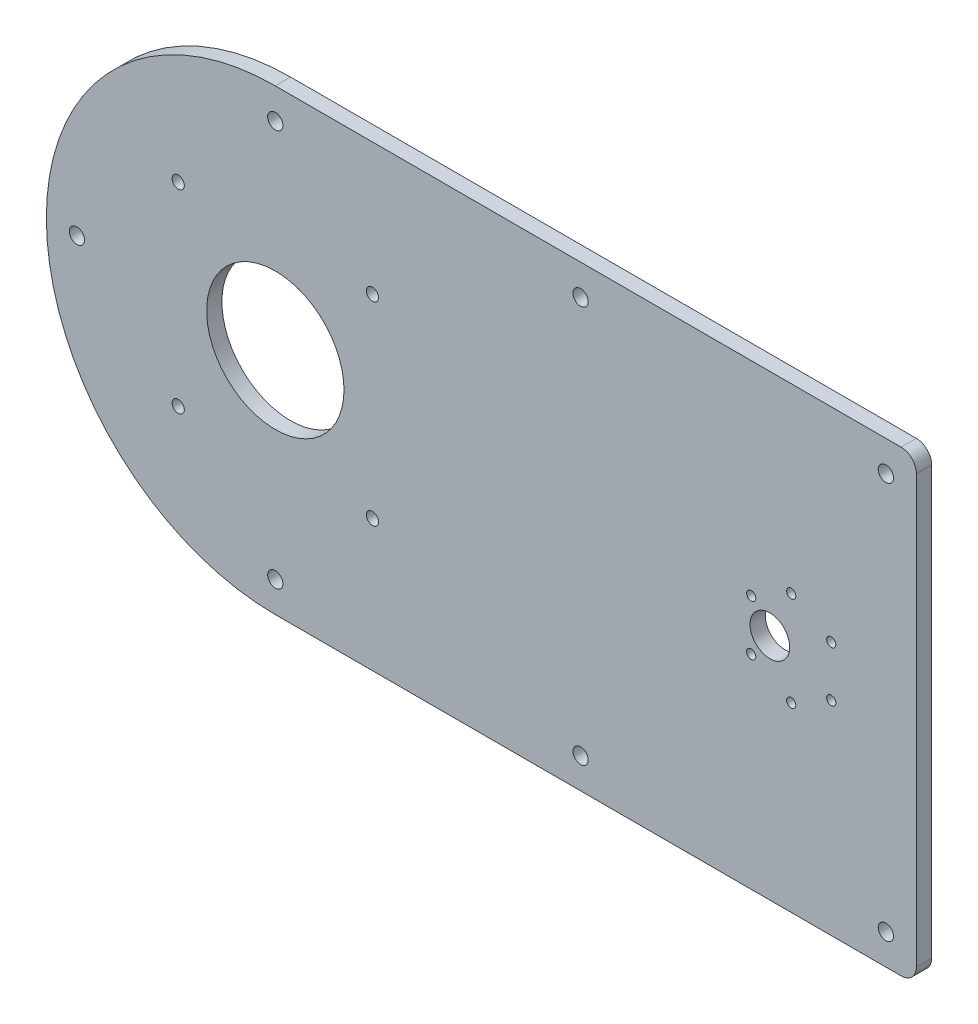
SolidWorks part; units mm, degrees
ref_plane "Front Plane" through (0, 0, 0) normal (0, 0, 1) x (1, 0, 0)
ref_plane "Top Plane" through (0, 0, 0) normal (0, 1, 0) x (1, 0, 0)
ref_plane "Right Plane" through (0, 0, 0) normal (1, 0, 0) x (0, 0, -1)
sketch "Sketch1" plane through (0, 0, 0) normal (0, 0, 1) x (1, 0, 0)
  line L1 (30.0007, 92.5455) -> (235.0007, 92.5455)
  line L3 (30.0007, -57.4545) -> (235.0007, -57.4545)
  line L4 (240.0007, 87.5455) -> (240.0007, -52.4545)
  arc A0 (235.0007, -57.4545) -> (240.0007, -52.4545) centre (235.0007, -52.4545) ccw
  arc A1 (235.0007, 92.5455) -> (240.0007, 87.5455) centre (235.0007, 87.5455) cw
  arc A2 (30.0007, 92.5455) -> (30.0007, -57.4545) centre (30.0007, 17.5455) ccw
  circle A7 centre (-34.9993, 17.5455) radius 2.5
  circle A10 centre (30.0007, -47.4545) radius 2.5
  circle A11 centre (30.0007, 82.5455) radius 2.5
  circle A12 centre (230.0007, -47.4545) radius 2.5
  circle A13 centre (230.0007, 82.5455) radius 2.5
  circle A15 centre (130.0007, 82.5455) radius 2.5
  circle A16 centre (130.0007, -47.4545) radius 2.5
  circle A18 centre (30.0007, 17.5455) radius 22.5
  circle A23 centre (61.8157, 49.3605) radius 2
  circle A24 centre (61.8157, -14.2695) radius 2
  circle A25 centre (-1.8143, -14.2695) radius 2
  circle A26 centre (-1.8143, 49.3605) radius 2
  circle A27 centre (192.0007, 17.5455) radius 6.5
  circle A31 centre (199.0007, 33.0455) radius 1.5
  circle A32 centre (199.0007, 2.0455) radius 1.5
  circle A33 centre (185.8934, 25.8189) radius 1.5
  circle A34 centre (212.108, 25.8189) radius 1.5
  circle A35 centre (212.108, 9.2721) radius 1.5
  circle A36 centre (185.8934, 9.2721) radius 1.5
  point P2 (30.0007, 17.5455)
  point P12 (192.0007, 17.5455)
  point P14 (30.0007, 17.5455)
  point P21 (-34.9993, 17.5455)
  point P23 (30.0007, 17.5455)
  point P53 (30.0007, 17.5455)
  point P54 (30.0007, 17.5455)
  dimension "D1" = 5
  dimension "D2" = 13
  dimension "D3" = 45
  dimension "D4" = 5
  dimension "D5" = 5
  dimension "D6" = 5
  dimension "D7" = 5
  dimension "D8" = 5
  dimension "D9" = 5
  dimension "D10" = 5
  dimension "D11" = 4
  dimension "D12" = 4
  dimension "D13" = 4
  dimension "D14" = 4
  dimension "D15" = 3
  dimension "D16" = 3
  dimension "D17" = 3
  dimension "D18" = 3
  dimension "D19" = 3
  dimension "D20" = 3
  dimension "D21" = 162
  dimension "D22" = 210
  dimension "D23" = 150
extrude "Boss-Extrude1" add sketch "Sketch1" along normal blind 5
